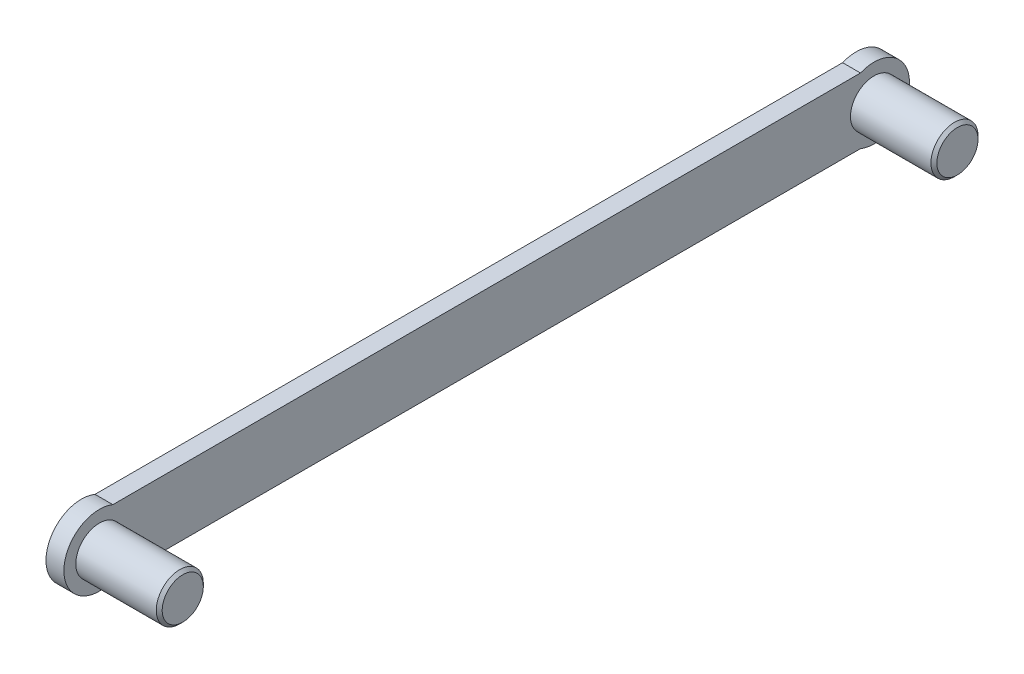
SolidWorks part; units mm, degrees
ref_plane "Front Plane" through (0, 0, 0) normal (0, 0, 1) x (1, 0, 0)
ref_plane "Top Plane" through (0, 0, 0) normal (0, 1, 0) x (1, 0, 0)
ref_plane "Right Plane" through (0, 0, 0) normal (1, 0, 0) x (0, 0, -1)
sketch "Sketch1" plane through (0, 0, 0) normal (1, 0, 0) x (0, 0, -1)
  line L0 (-89.172, -2.2228) -> (40.828, -2.2228) construction
  line L1 (-89.172, 3.2772) -> (40.828, 3.2772)
  line L2 (-89.172, 3.2772) -> (-89.172, -7.7228)
  line L3 (-89.172, -7.7228) -> (40.828, -7.7228)
  line L4 (40.828, 3.2772) -> (40.828, -7.7228)
  circle A0 centre (-89.172, -2.2228) radius 3.95
  circle A1 centre (-89.172, -2.2228) radius 5.95
  circle A2 centre (40.828, -2.2228) radius 3.95
  circle A3 centre (40.828, -2.2228) radius 5.95
  dimension "D1" = 7.9
  dimension "D2" = 2
  dimension "D3" = 130
  dimension "D4" = 11
extrude "Boss-Extrude1" add sketch "Sketch1" along normal blind 17 contours L2 A0 | L4 A2 | A2 L0 L4 | L0 A2 L4 | L0 L2 A0 | L2 L0 A0 region at (0, -0.5464, 87.4955) region at (0, -2.2228, 90.8484) region at (0, -3.8993, 87.4955) region at (0, -0.5464, -39.1516) region at (0, -3.8993, -39.1516) region at (0, -2.2228, -42.5045)
extrude "Boss-Extrude3" add sketch "Sketch1<4>" along normal blind 3 contours L0 A1 L3 A3 | A1 L0 A3 L1 | A0 L0 A1 L1 L2 | L0 A0 L2 L3 A1 | L2 A0 | L0 L2 A0 | L2 L0 A0 | L1 A1 L3 L2 A0 | L4 A2 | L0 A2 L4 | A2 L0 L4 | A3 L0 A2 L4 L1 | L3 A3 L1 L4 A2 | L0 A3 L3 L4 A2 region at (0, -0.5464, 87.4955) region at (0, -2.2228, 90.8484) region at (0, -3.8993, 87.4955) region at (0, 0.8565, 85.8699) region at (0, -5.3022, 85.8699) region at (0, -2.2228, 93.2666) region at (0, 0.5522, 24.172) region at (0, -4.9978, 24.172) region at (0, 0.8565, -37.5259) region at (0, -5.3022, -37.5259) region at (0, -0.5464, -39.1516) region at (0, -3.8993, -39.1516) region at (0, 2.6021, -44.0564) region at (0, -2.2228, -42.5045)
sketch "Sketch1<4>" plane through (0, 0, 0) normal (1, 0, 0) x (0, 0, -1) same geometry as "Sketch1"
ref_plane "Plane1" through (17, 0, 0) normal (1, 0, 0) x (0, 0, -1)
chamfer "Chamfer1" distance 0.5 angle 45 2 edges at (17, -2.2228, 85.222) (17, -2.2228, -44.778)
